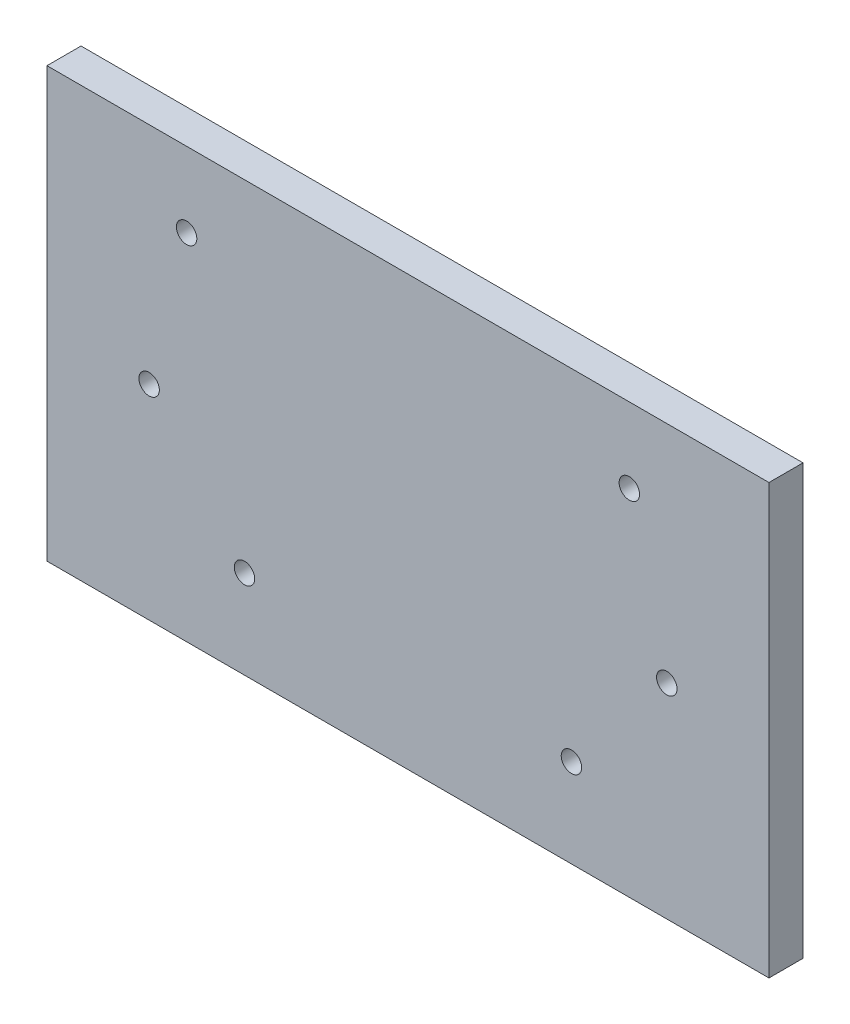
SolidWorks part; units mm, degrees
ref_plane "Front" through (0, 0, 0) normal (0, 0, 1) x (1, 0, 0)
ref_plane "Top" through (0, 0, 0) normal (0, 1, 0) x (1, 0, 0)
ref_plane "Right" through (0, 0, 0) normal (1, 0, 0) x (0, 0, -1)
sketch "Sketch1" plane through (0, 0, 0) normal (0, 0, 1) x (1, 0, 0)
  line L1 (-53, 31.5) -> (53, 31.5)
  line L2 (-53, 31.5) -> (-53, -31.5)
  line L3 (-53, -31.5) -> (53, -31.5)
  line L4 (53, 31.5) -> (53, -31.5)
  line L5 (-53, 31.5) -> (53, -31.5) construction
  line L6 (-53, -31.5) -> (53, 31.5) construction
  point P0 (0, 0)
  dimension "D1" = 63
  dimension "D2" = 106
extrude "Boss-Extrude1" add sketch "Sketch1" along normal blind 5
sketch "Sketch2" plane through (0, 0, 0) normal (0, 0, 1) x (1, 0, 0)
  line L0 (-53, -31.5) -> (53, -31.5) construction
  line L1 (0, 31.5) -> (0, -31.5) construction
  line L2 (53, 31.5) -> (-53, 31.5) construction
  circle A0 centre (-24, -18.5) radius 1.5
  circle A1 centre (24, -18.5) radius 1.5
  circle A2 centre (-38, -1.5) radius 1.5
  circle A3 centre (38, -1.5) radius 1.5
  circle A4 centre (-32.5, 20.5) radius 1.5
  circle A5 centre (32.5, 20.5) radius 1.5
  dimension "D1" = 3
  dimension "D2" = 3
  dimension "D6" = 3
  dimension "D7" = 3
  dimension "D11" = 3
  dimension "D12" = 3
  dimension "D3" = 13
  dimension "D4" = 48
  dimension "D5" = 24
  dimension "D8" = 76
  dimension "D9" = 38
  dimension "D10" = 30
  dimension "D13" = 11
  dimension "D14" = 65
  dimension "D15" = 32.5
extrude "Cut-Extrude2" cut sketch "Sketch2" along normal through all
ref_plane "Plane1" through (0, -31.5, 0) normal (0, -1, 0) x (-1, 0, 0)
equation "\"D5@Sketch2\"= \"D4@Sketch2\" / 2"
equation "\"D9@Sketch2\"= \"D8@Sketch2\" / 2"
equation "\"D15@Sketch2\"= \"D14@Sketch2\" / 2"
